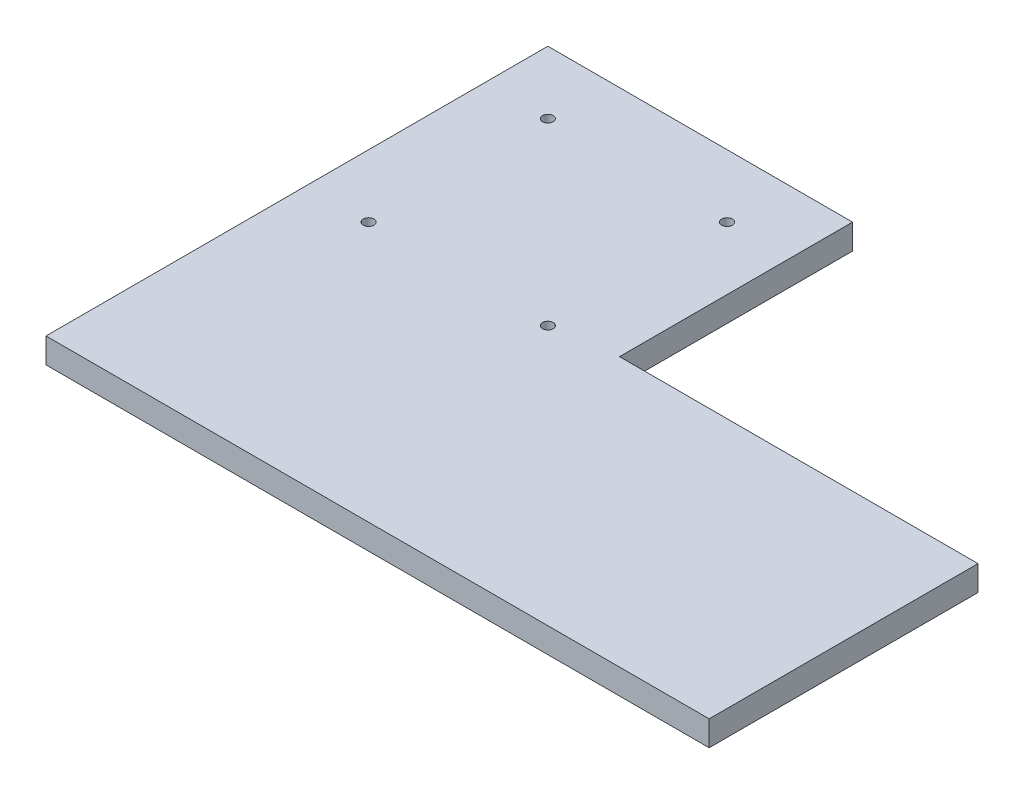
SolidWorks part; units mm, degrees
ref_plane "Front Plane" through (0, 0, 0) normal (0, 0, 1) x (1, 0, 0)
ref_plane "Top Plane" through (0, 0, 0) normal (0, 1, 0) x (1, 0, 0)
ref_plane "Right Plane" through (0, 0, 0) normal (1, 0, 0) x (0, 0, -1)
sketch "Sketch1" plane through (0, 0, 0) normal (0, 1, 0) x (1, 0, 0)
  line L0 (14.3183, 31.8949) -> (-70.6817, 31.8949)
  line L1 (-70.6817, 31.8949) -> (-70.6817, -108.1051)
  line L2 (-70.6817, -108.1051) -> (114.3183, -108.1051)
  line L3 (114.3183, -108.1051) -> (114.3183, -33.1051)
  line L4 (114.3183, -33.1051) -> (14.3183, -33.1051)
  line L5 (14.3183, -33.1051) -> (14.3183, 31.8949)
  dimension "D1" = 65
  dimension "D2" = 85
  dimension "D3" = 140
  dimension "D4" = 185
extrude "Boss-Extrude1" add sketch "Sketch1" along normal blind 7 contours L5 L0 L1 L2 L3 L4
ref_plane "Plane1" through (0, 7, 0) normal (0, 1, 0) x (1, 0, 0)
sketch "Sketch2" plane through (0, 7, 0) normal (0, 1, 0) x (1, 0, 0)
  line L0 (14.3183, 31.8949) -> (-70.6817, 31.8949) construction
  line L1 (-58.1817, 19.3949) -> (1.8183, 19.3949)
  line L2 (-58.1817, 19.3949) -> (-58.1817, -40.6051)
  line L3 (-58.1817, -40.6051) -> (1.8183, -40.6051)
  line L4 (1.8183, 19.3949) -> (1.8183, -40.6051)
  line L5 (-70.6817, 31.8949) -> (-70.6817, -108.1051) construction
  line L6 (-53.1817, 19.3949) -> (-53.1817, -40.6051) construction
  line L7 (-58.1817, 14.3949) -> (1.8183, 14.3949) construction
  line L8 (-58.1817, -10.6051) -> (1.8183, -10.6051) construction
  circle A0 centre (-53.1817, 14.3949) radius 1.5
  circle A1 centre (-3.1817, 14.3949) radius 1.5
  circle A2 centre (-3.1817, -35.6051) radius 1.5
  circle A3 centre (-53.1817, -35.6051) radius 1.5
  dimension "D7" = 2
  dimension "D8" = 3
  dimension "D1" = 60
  dimension "D2" = 60
  dimension "D3" = 12.5
  dimension "D4" = 12.5
  dimension "D5" = 5
  dimension "D6" = 5
extrude "Cut-Extrude2" cut sketch "Sketch2" against normal through all contours A0 | A2 | A3 | A1
